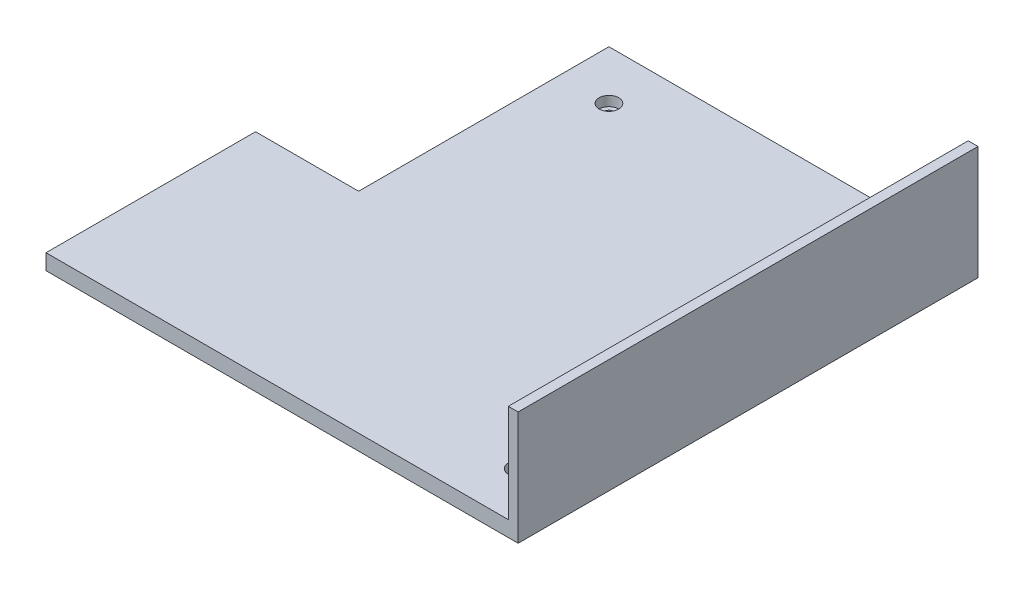
SolidWorks part; units mm, degrees
ref_plane "Front Plane" through (0, 0, 0) normal (0, 0, 1) x (1, 0, 0)
ref_plane "Top Plane" through (0, 0, 0) normal (0, 1, 0) x (1, 0, 0)
ref_plane "Right Plane" through (0, 0, 0) normal (1, 0, 0) x (0, 0, -1)
sketch "Sketch1" plane through (0, 0, 0) normal (0, 1, 0) x (1, 0, 0)
  line L1 (-96.2, 93.7) -> (96.2, 93.7)
  line L2 (-96.2, 93.7) -> (-96.2, -93.7)
  line L3 (-96.2, -93.7) -> (96.2, -93.7)
  line L4 (96.2, 93.7) -> (96.2, -93.7)
  line L5 (-96.2, 93.7) -> (96.2, -93.7) construction
  line L6 (-96.2, -93.7) -> (96.2, 93.7) construction
  point P0 (0, 0)
  dimension "D1" = 187.4
  dimension "D2" = 192.4
extrude "Boss-Extrude1" add sketch "Sketch1" along normal blind 6.35
sketch "Sketch2" plane through (0, 6.35, 0) normal (0, 1, 0) x (1, 0, 0)
  line L2 (-92.2, 89.7) -> (-92.2, -89.7)
  line L4 (96.2, -93.7) -> (96.2, 93.7)
  line L5 (96.2, 93.7) -> (-96.2, 93.7)
  line L6 (-96.2, 93.7) -> (-96.2, -93.7)
  line L7 (-96.2, -93.7) -> (96.2, -93.7)
  line L10 (-96.2, 93.7) -> (-96.2, -93.7)
  line L12 (92.2, 89.7) -> (-92.2, 89.7) construction
  line L13 (96.2, 93.7) -> (-96.2, 93.7) construction
  line L14 (92.2, -89.7) -> (92.2, 89.7) construction
  line L15 (96.2, -93.7) -> (96.2, 93.7) construction
  line L16 (-92.2, 89.7) -> (-92.2, 93.7)
  line L17 (96.2, 93.7) -> (-96.2, 93.7) construction
  line L18 (-92.2, 93.7) -> (-96.2, 93.7)
  line L22 (-92.2, -89.7) -> (92.2, -89.7) construction
  line L23 (-96.2, -93.7) -> (96.2, -93.7) construction
  line L24 (-92.2, -89.7) -> (-92.2, -93.7)
  line L25 (-96.2, -93.7) -> (96.2, -93.7) construction
  line L26 (-92.2, -93.7) -> (-96.2, -93.7)
  dimension "D1" = 0
  dimension "D2" = 4
extrude "Boss-Extrude2" add sketch "Sketch2" along normal blind 40
sketch "Sketch4" plane through (0, 6.35, 0) normal (0, 1, 0) x (1, 0, 0)
  line L0 (-92.2, -93.7) -> (96.2, -93.7) construction
  line L1 (96.2, 93.7) -> (54.2, 93.7)
  line L2 (96.2, 93.7) -> (96.2, -8.3)
  line L3 (96.2, -8.3) -> (54.2, -8.3)
  line L4 (54.2, 93.7) -> (54.2, -8.3)
  line L5 (-96.2, 93.7) -> (-96.2, -93.7) construction
  dimension "D1" = 85.4
  dimension "D2" = 150.4
extrude "Cut-Extrude1" cut sketch "Sketch4" against normal up to next
sketch "Sketch5" plane through (0, 6.35, 0) normal (0, 1, 0) x (1, 0, 0)
  line L0 (-96.2, 93.7) -> (-96.2, -93.7) construction
  line L1 (54.2, 93.7) -> (-96.2, 93.7) construction
  line L2 (54.2, 93.7) -> (54.2, 53.7) construction
  line L3 (54.2, 53.7) -> (-96.2, 53.7) construction
  line L4 (-96.2, 93.7) -> (-96.2, 53.7) construction
  line L5 (-92.2, -93.7) -> (96.2, -93.7) construction
  line L6 (-96.2, 93.7) -> (-56.2, 93.7) construction
  line L7 (-96.2, 93.7) -> (-96.2, -93.7) construction
  line L8 (-96.2, -93.7) -> (-56.2, -93.7) construction
  line L9 (-56.2, 93.7) -> (-56.2, -93.7) construction
  line L10 (-76.2, -93.7) -> (-76.2, 93.7) construction
  line L11 (54.2, 73.7) -> (-96.2, 73.7) construction
  point P18 (-76.2, 73.7)
  point P20 (-76.2, -73.7)
  point P24 (34.2, 73.7)
  dimension "D1" = 40
  dimension "D2" = 40
  dimension "D3" = 20
  dimension "D4" = 20
hole_wizard "CBORE for M4 SHCS1" positions "Sketch5" profile "Sketch6" counterbore size "M4" standard "ANSI Metric" end condition up to next
sketch "Sketch6" plane through (34.2, 6.35, -73.7) normal (1, 0, 0) x (0, 0, 1)
  line L0 (0, 0) -> (0, 6.35)
  line L1 (0, 6.35) -> (2.25, 6.35)
  line L3 (2.25, 6.35) -> (2.25, 4)
  line L4 (2.25, 4) -> (4, 4)
  line L5 (4, 4) -> (4, 0)
  line L7 (4, 0) -> (0, 0)
  line L11 (0, -6.35) -> (0, 107.95) construction
  dimension "Thru Hole Dia." = 4.5
  dimension "Thru Hole Depth" = 6.35
  dimension "C'Bore Dia." = 8
  dimension "C'Bore Depth" = 4
mirror "Mirror1" about plane through (96.2, 6.35, -93.7) normal (-1, 0, 0) of bodies 105
delete or keep bodies "Body-Delete/Keep 1" type delete bodies bodies 105
equation "\"D2@Sketch1\"=384.8/2"
equation "\"D2@Sketch4\"=152.4-2"
equation "\"D1@Sketch4\"=87.4-2"
